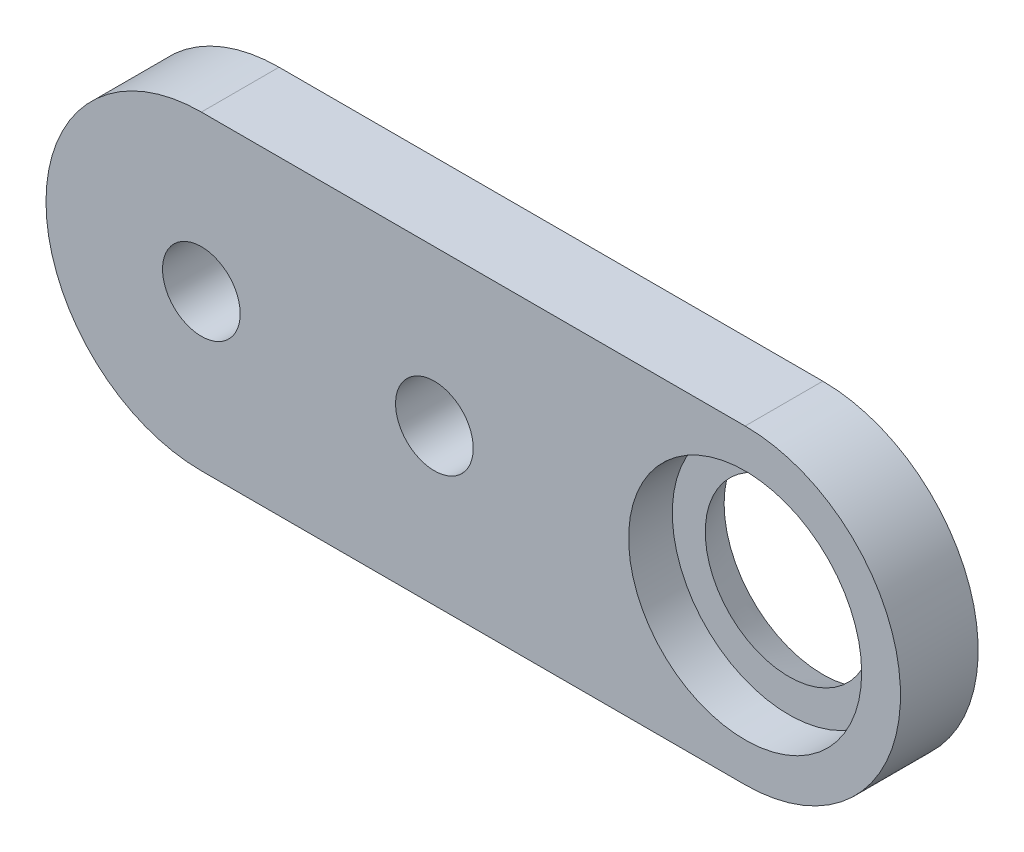
SolidWorks part; units mm, degrees
ref_plane "Front Plane" through (0, 0, 0) normal (0, 0, 1) x (1, 0, 0)
ref_plane "Top Plane" through (0, 0, 0) normal (0, 1, 0) x (1, 0, 0)
ref_plane "Right Plane" through (0, 0, 0) normal (1, 0, 0) x (0, 0, -1)
sketch "Sketch1" plane through (0, 0, 0) normal (0, 0, 1) x (1, 0, 0)
  line L0 (0, -12.7) -> (69.85, -12.7) construction
  line L1 (0, -25.4) -> (69.85, -25.4)
  line L2 (0, -25.4) -> (0, 0)
  line L3 (0, 0) -> (69.85, 0)
  line L4 (69.85, -25.4) -> (69.85, 0)
  circle A0 centre (57.15, -12.7) radius 9.525
  circle A1 centre (57.15, -12.7) radius 6.35
  circle A2 centre (12.7, -12.7) radius 3.175
  circle A3 centre (31.75, -12.7) radius 3.175
  point P0 (57.15, -12.7)
  dimension "D2" = 19.05
  dimension "D3" = 12.7
  dimension "D5" = 6.35
  dimension "D1" = 25.4
  dimension "D6" = 12.7
  dimension "D7" = 25.4
  dimension "D8" = 19.05
  dimension "D9" = 12.7
extrude "Boss-Extrude2" add sketch "Sketch1" along normal blind 6.35 contours L1 L4 L3 L2 A3 A2 A0 | L0 L2 L1 L4 A0 A3 A2 region at (31.0464, -5.6665, 0) region at (31.0464, -19.7335, 0)
extrude "Boss-Extrude3" add sketch "Sketch1<5>" along normal blind 2.7781 contours A0 A1 | L0 A0 A1 region at (57.15, -6.137, 0) region at (65.0875, -12.913, 0)
sketch "Sketch1<5>" plane through (0, 0, 0) normal (0, 0, 1) x (1, 0, 0) same geometry as "Sketch1"
fillet "Fillet1" radius 12.7 2 edges at (0, -25.4, 3.175) (0, 0, 3.175)
sketch "Sketch2" plane through (0, 0, 6.35) normal (0, 0, 1) x (1, 0, 0)
  line L0 (12.7, 0) -> (69.85, 0) construction
  line L1 (44.45, -25.4) -> (69.85, -25.4)
  line L2 (44.45, -25.4) -> (44.45, 0)
  line L3 (44.45, 0) -> (69.85, 0)
  line L4 (69.85, -25.4) -> (69.85, 0)
  line L5 (44.45, -25.4) -> (69.85, 0) construction
  line L6 (44.45, 0) -> (69.85, -25.4) construction
  circle A0 centre (57.15, -12.7) radius 12.7
  point P0 (57.15, -12.7)
  line M13 (69.85, -25.4) -> (69.85, 0)
  line M15 (69.85, 0) -> (12.7, 0)
extrude "Cut-Extrude1" cut sketch "Sketch2" against normal through all contours A0 L4 M15 | A0 L1 M13 region at (67.0132, -22.5632, 6.35) region at (67.0132, -2.8368, 6.35)
ref_axis "Axis1" through (57.15, -12.7, 2.7781) along (0, 0, -1)
ref_plane "Plane1" through (57.15, 0, 0) normal (1, 0, 0) x (0, 0, -1)
sketch "Sketch3" plane through (57.15, 0, 0) normal (1, 0, 0) x (0, 0, -1)
  line L0 (0, -12.7) -> (-6.35, -12.7)
  line L8 (0, -25.4) -> (0, 0) construction
  line L9 (-6.35, 0) -> (-6.35, -25.4) construction
  line L10 (-6.35, -12.7) -> (1.9474, -9.0058)
  line L11 (1.9474, -9.0058) -> (0, -4.6318)
  line L12 (0, -4.6318) -> (-8.2974, -8.326)
  line L13 (-8.2974, -8.326) -> (-6.35, -12.7)
  line L14 (0, -12.7) -> (0, -6.35)
  line L15 (0, -6.35) -> (-2.7781, -6.35)
  line L16 (-2.7781, -6.35) -> (-2.7781, -12.7)
  line L17 (0, -6.35) -> (0, -4.6318)
  line L18 (-2.7781, -6.35) -> (-2.7781, -5.8687)
  dimension "D1" = 4.7879
  dimension "D2" = 6.35
  dimension "D3" = 24
  dimension "D4" = 2.7781
revolve "Cut-Revolve3" cut sketch "Sketch3" angle 360 about axis through (57.15, -12.7, 2.7781) along (0, 0, -1) region at (57.15, -8.436, 1.4582) region at (57.15, -5.7422, 1.1287)
